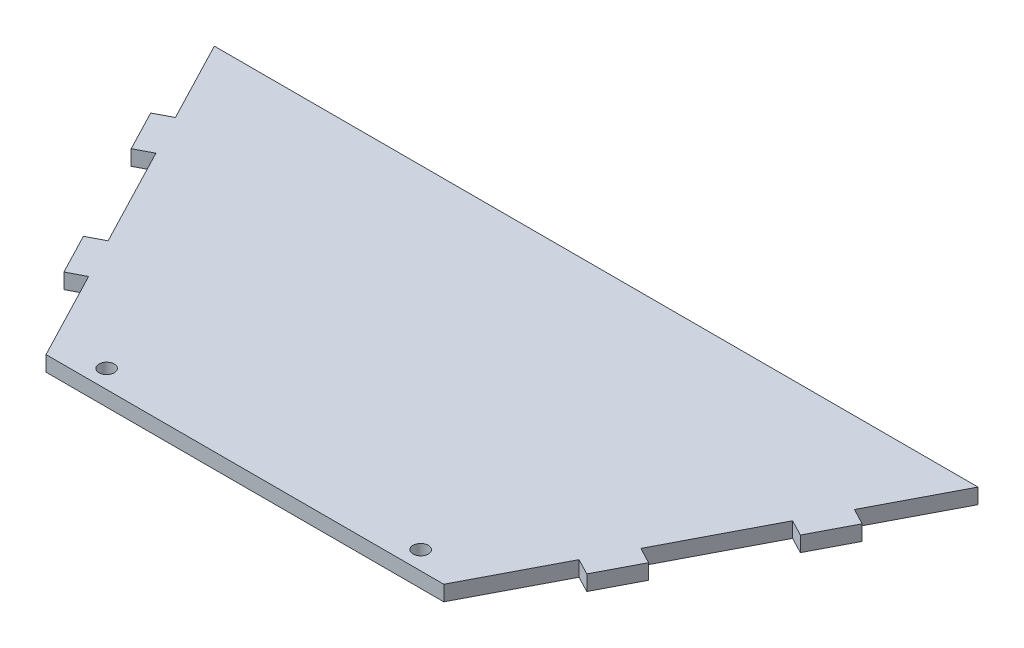
SolidWorks part; units mm, degrees
ref_plane "前视基准面" through (0, 0, 0) normal (0, 0, 1) x (1, 0, 0)
ref_plane "上视基准面" through (0, 0, 0) normal (0, 1, 0) x (1, 0, 0)
ref_plane "右视基准面" through (0, 0, 0) normal (1, 0, 0) x (0, 0, -1)
sketch "草图1" plane through (0, 0, 0) normal (0, 1, 0) x (1, 0, 0)
  line L1 (-65.115, -61.128) -> (65.115, -61.128)
  line L2 (-65.115, -61.128) -> (-80.2726, -32.0201)
  line L3 (-125, 53.872) -> (125, 53.872)
  line L4 (65.115, -61.128) -> (80.2726, -32.0201)
  line L20 (-111.1439, 27.2635) -> (-116.4656, 24.4923)
  line L21 (-116.4656, 24.4923) -> (-109.5376, 11.1881)
  line L22 (-109.5376, 11.1881) -> (-104.2159, 13.9593)
  line L23 (-87.2007, -18.7159) -> (-92.5224, -21.4871)
  line L24 (-92.5224, -21.4871) -> (-85.5943, -34.7913)
  line L25 (-85.5943, -34.7913) -> (-80.2726, -32.0201)
  line L26 (111.1439, 27.2635) -> (116.4656, 24.4923)
  line L27 (116.4656, 24.4923) -> (109.5376, 11.1881)
  line L28 (109.5376, 11.1881) -> (104.2159, 13.9593)
  line L29 (87.2007, -18.7159) -> (92.5224, -21.4871)
  line L30 (92.5224, -21.4871) -> (85.5943, -34.7913)
  line L31 (85.5943, -34.7913) -> (80.2726, -32.0201)
  line L32 (-111.1439, 27.2635) -> (-125, 53.872)
  line L33 (-87.2007, -18.7159) -> (-104.2159, 13.9593)
  line L34 (87.2007, -18.7159) -> (104.2159, 13.9593)
  line L35 (111.1439, 27.2635) -> (125, 53.872)
  point P0 (0, 0)
  point P6 (0, 53.872)
  point P7 (0, -61.128)
  dimension "D2" = 250
  dimension "D3" = 6
  dimension "D4" = 15
  dimension "D5" = 6
  dimension "D6" = 15
  dimension "D7" = 30
  dimension "D8" = 36.84
  dimension "D9" = 6
  dimension "D10" = 15
  dimension "D11" = 6
  dimension "D12" = 15
  dimension "D13" = 36.84
  dimension "D14" = 30
  dimension "D15" = 130.23
  dimension "D19" = 115
extrude "凸台-拉伸1" add sketch "草图1" along normal blind 5
sketch "草图2" plane through (0, 5, 0) normal (0, 1, 0) x (1, 0, 0)
  line L0 (-65.115, -61.128) -> (65.115, -61.128) construction
  circle A0 centre (-51.275, -55.118) radius 2.5
  circle A1 centre (51.525, -55.118) radius 2.5
  dimension "D1" = 5
  dimension "D2" = 5
  dimension "D3" = 6.01
  dimension "D4" = 6.01
  dimension "D5" = 13.84
  dimension "D6" = 13.59
extrude "切除-拉伸1" cut sketch "草图2" against normal blind 10
